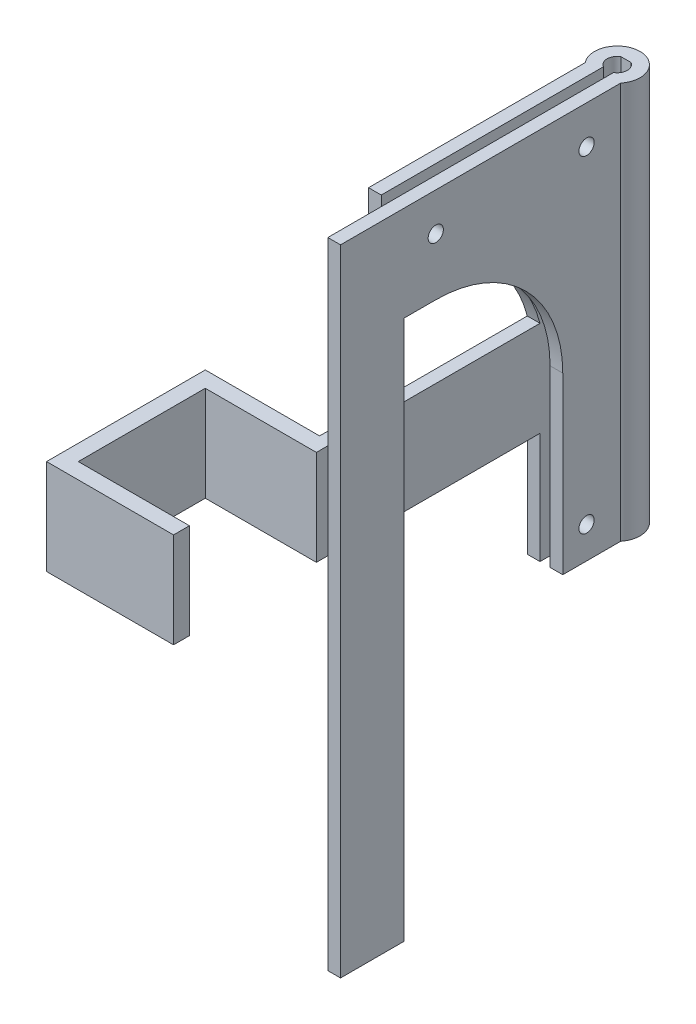
SolidWorks part; units mm, degrees
ref_plane "Front Plane" through (0, 0, 0) normal (0, 0, 1) x (1, 0, 0)
ref_plane "Top Plane" through (0, 0, 0) normal (0, 1, 0) x (1, 0, 0)
ref_plane "Right Plane" through (0, 0, 0) normal (1, 0, 0) x (0, 0, -1)
sketch "Sketch1" plane through (0, 0, 0) normal (0, 1, 0) x (1, 0, 0)
  line L0 (-1.5875, -2.7496) -> (-1.5875, -22.7496)
  line L1 (1.5875, -2.7496) -> (1.5875, -22.7496)
  line L2 (1.5875, 2.7496) -> (-1.5875, 2.7496)
  line L3 (5.5875, -4.5012) -> (5.5875, -22.7496)
  line L4 (-5.5875, -4.5012) -> (-5.5875, -22.7496)
  line L5 (-5.5875, -22.7496) -> (-1.5875, -22.7496)
  line L6 (1.5875, -22.7496) -> (5.5875, -22.7496)
  arc A0 (1.5875, -2.7496) -> (1.5875, 2.7496) centre (0, 0) ccw
  arc A1 (5.5875, -4.5012) -> (-5.5875, -4.5012) centre (0, 0) ccw
  arc A2 (-1.5875, 2.7496) -> (-1.5875, -2.7496) centre (0, 0) ccw
  arc A4 (1.5875, -2.7496) -> (-1.5875, -2.7496) centre (0, 0) ccw construction
  dimension "D1" = 3.175
  dimension "D2" = 20
  dimension "D3" = 3.175
  dimension "D5" = 3.175
  dimension "D4" = 4
extrude "Boss-Extrude1" add sketch "Sketch1" along normal blind 125
sketch "Sketch5" plane through (0, 125, 0) normal (0, 1, 0) x (1, 0, 0)
  line L1 (-1.5875, -93.175) -> (-1.5875, -88.175)
  line L2 (-41.5875, -88.175) -> (-41.5875, -138.175)
  line L3 (-41.5875, -138.175) -> (-1.5875, -138.175)
  line L4 (-1.5875, -138.175) -> (-1.5875, -133.175)
  line L5 (-1.5875, -133.175) -> (-36.5875, -133.175)
  line L9 (-1.5875, -22.7496) -> (-1.5875, -2.7496) construction
  line L10 (-36.5875, -93.175) -> (-1.5875, -93.175)
  line L12 (-36.5875, -133.175) -> (-36.5875, -93.175)
  line L13 (-41.5875, -88.175) -> (-1.5875, -88.175)
  line L18 (-18.6703, -3.175) -> (17.7565, -3.175) construction
  circle A0 centre (0, 0) radius 3.175 construction
  arc A1 (-1.5875, 2.7496) -> (-1.5875, -2.7496) centre (0, 0) ccw construction
  point P2 (-36.5875, -113.175)
  dimension "D2" = 110
  dimension "D1" = 35
  dimension "D3" = 40
  dimension "D4" = 5
  dimension "D5" = 5
  dimension "D7" = 5
extrude "Boss-Extrude2" add sketch "Sketch5" against normal mid plane 30 from offset 75 offset against normal yes
sketch "Sketch6" plane through (0, 125, 0) normal (0, 1, 0) x (1, 0, 0)
  line L0 (5.5875, -22.7496) -> (5.5875, -4.5012) construction
  line L1 (1.5875, -22.7496) -> (5.5875, -22.7496)
  line L2 (1.5875, -22.7496) -> (1.5875, -72.7496)
  line L3 (1.5875, -72.7496) -> (5.5875, -72.7496)
  line L4 (5.5875, -22.7496) -> (5.5875, -72.7496)
  line L6 (-1.5875, -22.7496) -> (-1.5875, -2.7496) construction
  line L7 (-5.5875, -22.7496) -> (-1.5875, -22.7496)
  line L8 (-5.5875, -22.7496) -> (-5.5875, -72.7496)
  line L9 (-5.5875, -72.7496) -> (-1.5875, -72.7496)
  line L10 (-1.5875, -22.7496) -> (-1.5875, -72.7496)
  dimension "D1" = 50
extrude "Boss-Extrude3" add sketch "Sketch6" against normal blind 30
hole_wizard "M4 Clearance Hole1" positions "Sketch2" profile "Sketch3" hole size "M4" standard "ANSI Metric" end condition through all
sketch "Sketch2" plane through (5.5875, 0, 0) normal (1, 0, 0) x (0, 0, -1)
  line L4 (-72.7496, 125) -> (-4.5012, 125) construction
  line L6 (-72.7496, 95) -> (-72.7496, 125) construction
  point P0 (-15.2496, 113)
  point P4 (-15.2496, 10)
  point P19 (-62.7496, 113)
  dimension "D1" = 103
  dimension "D2" = 12
  dimension "D3" = 47.5
  dimension "D4" = 10
sketch "Sketch3" plane through (5.5875, 113, 15.2496) normal (0, 1, 0) x (0, 0, -1)
  line L0 (0, 0) -> (0, 47.175)
  line L1 (0, 47.175) -> (2.4, 47.175)
  line L2 (2.4, 47.175) -> (2.4, 0)
  line L5 (2.4, 0) -> (0, 0)
  line L11 (0, -6.35) -> (0, 107.95) construction
  dimension "Thru Hole Dia." = 4.8
  dimension "Thru Hole Depth" = 47.175
sketch "Sketch9" plane through (-1.5875, 0, 0) normal (1, 0, 0) x (0, 0, -1)
  line L0 (-88.175, 65) -> (-22.7496, 65)
  line L1 (-88.175, 65) -> (-88.175, 35)
  line L2 (-88.175, 35) -> (-22.7496, 35)
  line L3 (-22.7496, 95) -> (-22.7496, 0) construction
  line L4 (-22.7496, 35) -> (-22.7496, 65)
extrude "Boss-Extrude5" add sketch "Sketch9" against normal up to surface (4 mm away) up to face at (-5.5875, 113, 12.8496)
chamfer "Chamfer2" [suppressed] distance 36 angle 45
fillet "Fillet1" radius 40 2 edges at (3.5875, 95, 22.7496) (-3.5875, 95, 22.7496)
fillet "Fillet2" [suppressed] radius 10
sketch "Sketch12" plane through (5.5875, 0, 0) normal (1, 0, 0) x (0, 0, -1)
  line L0 (-72.7496, 125) -> (-92.7496, 125)
  line L1 (-92.7496, 125) -> (-92.7496, -75)
  line L2 (-92.7496, -75) -> (-72.7496, -75)
  line L3 (-72.7496, -75) -> (-72.7496, 125)
  dimension "D1" = 200
  dimension "D2" = 20
extrude "Boss-Extrude6" add sketch "Sketch12" against normal up to surface (4 mm away) up to face at (1.5875, 113, 12.8496)
ref_plane "Plane1" through (0, 0, 0) normal (-1, 0, 0) x (0, 0, 1)
ref_plane "Plane2" through (0, -15, 0) normal (0, 1, 0) x (1, 0, 0)
ref_axis "Axis1" through (0, -15, 97.6963) along (0, 0, -1)
sketch "Sketch13" plane through (0, 125, 0) normal (0, 1, 0) x (1, 0, 0)
  line L0 (-1.5875, -93.175) -> (-1.5875, -88.175)
  line L1 (-41.5875, -88.175) -> (-41.5875, -138.175)
  line L2 (-41.5875, -138.175) -> (-1.5875, -138.175)
  line L3 (-1.5875, -138.175) -> (-1.5875, -133.175)
  line L4 (-1.5875, -133.175) -> (-36.5875, -133.175)
  line L5 (-36.5875, -93.175) -> (-1.5875, -93.175)
  line L6 (-36.5875, -133.175) -> (-36.5875, -93.175)
  line L7 (-41.5875, -88.175) -> (-1.5875, -88.175)
  line L8 (-18.6703, -3.175) -> (17.7565, -3.175) construction
  line L9 (-1.5875, -22.7496) -> (-1.5875, -93.175) construction
  circle A0 centre (0, 0) radius 3.175 construction
  arc A1 (1.5875, -2.7496) -> (1.5875, 2.7496) centre (0, 0) ccw construction
  dimension "D1" = 85
  dimension "D2" = 5
  dimension "D3" = 5
  dimension "D4" = 40
  dimension "D5" = 35
  dimension "D6" = 40
